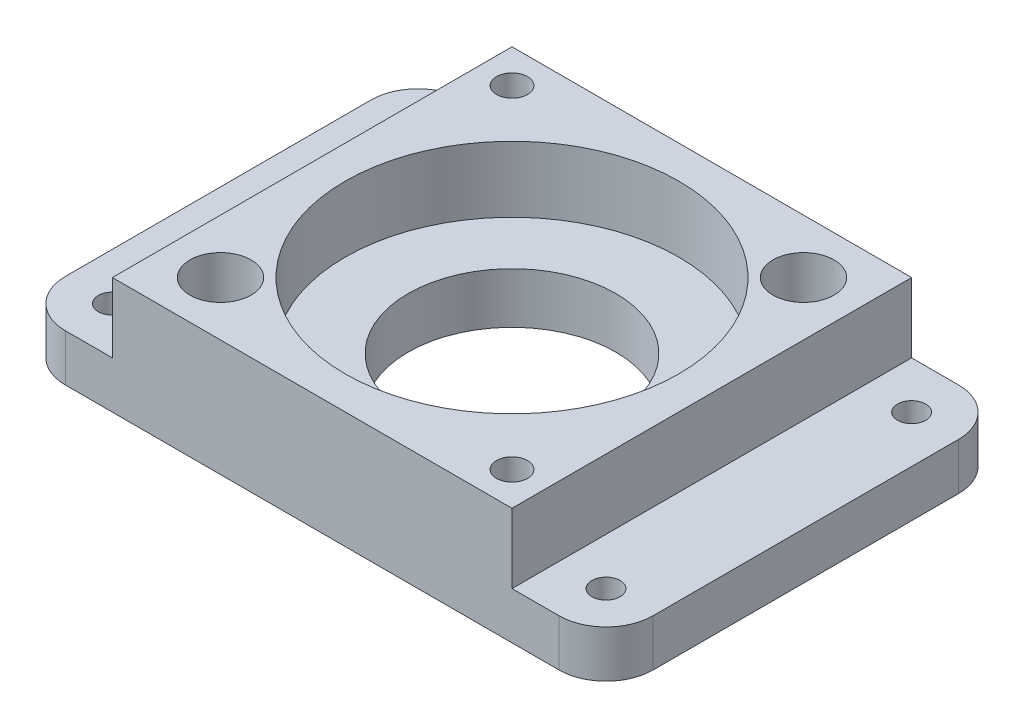
SolidWorks part; units mm, degrees
ref_plane "前视基准面" through (0, 0, 0) normal (0, 0, 1) x (1, 0, 0)
ref_plane "上视基准面" through (0, 0, 0) normal (0, 1, 0) x (1, 0, 0)
ref_plane "右视基准面" through (0, 0, 0) normal (1, 0, 0) x (0, 0, -1)
sketch "草图1" plane through (0, 0, 0) normal (0, 1, 0) x (1, 0, 0)
  line L1 (0, 0) -> (42.5, 0)
  line L2 (0, 0) -> (0, 42.5)
  line L3 (0, 42.5) -> (42.5, 42.5)
  line L4 (42.5, 0) -> (42.5, 42.5)
  dimension "D1" = 42.5
extrude "凸台-拉伸1" add sketch "草图1" along normal blind 12.4 contours L1 L4 L3 L2 region at (21.25, 0, -21.25)
sketch "草图2" plane through (0, 12.4, 0) normal (0, 1, 0) x (1, 0, 0)
  line L0 (0, 21.25) -> (42.5, 21.25) construction
  line L1 (0, 0) -> (0, 42.5) construction
  line L2 (42.5, 0) -> (42.5, 42.5) construction
  circle A0 centre (21.25, 21.25) radius 17.75
  dimension "D1" = 35.5
extrude "切除-拉伸1" cut sketch "草图2" against normal blind 7
sketch "草图3" plane through (0, 5.4, 0) normal (0, 1, 0) x (1, 0, 0)
  circle A0 centre (21.25, 21.25) radius 11.05
  dimension "D1" = 22.1
extrude "切除-拉伸2" cut sketch "草图3" against normal through all
sketch "草图4" plane through (0, 12.4, 0) normal (0, 1, 0) x (1, 0, 0)
  line L0 (21.25, 21.25) -> (0, 42.5) construction
  line L2 (21.25, 21.25) -> (38.9277, 3.5723) construction
  line L4 (5.75, 5.75) -> (36.75, 5.75) construction
  line L5 (5.75, 5.75) -> (5.75, 36.75) construction
  line L6 (5.75, 36.75) -> (36.75, 36.75) construction
  line L7 (36.75, 5.75) -> (36.75, 36.75) construction
  line L8 (5.75, 5.75) -> (36.75, 36.75) construction
  line L9 (5.75, 36.75) -> (36.75, 5.75) construction
  circle A0 centre (21.25, 21.25) radius 25 construction
  circle A1 centre (3.5723, 38.9277) radius 1.65
  circle A2 centre (38.9277, 3.5723) radius 1.65
  circle A3 centre (36.75, 36.75) radius 3.25
  circle A4 centre (5.75, 5.75) radius 3.25
  circle A5 centre (5.75, 5.75) radius 1.525
  circle A6 centre (36.75, 36.75) radius 1.525
  dimension "D1" = 50
  dimension "D2" = 3.3
  dimension "D5" = 6.5
  dimension "D6" = 3.05
  dimension "D4" = 31
  dimension "D3" = 2
extrude "切除-拉伸3" cut sketch "草图4" against normal blind 10 contours A4 A5 | A5 | A6 | A3 A6 region at (33.5919, 12.4, -36.75) region at (2.5919, 12.4, -5.75) region at (5.75, 12.4, -5.75) region at (36.75, 12.4, -36.75)
extrude "切除-拉伸4" cut sketch "草图4<3>" against normal through all contours A5 | A2 | A6 | A1 region at (3.5723, 12.4, -38.9277) region at (38.9277, 12.4, -3.5723) region at (5.75, 12.4, -5.75) region at (36.75, 12.4, -36.75)
sketch "草图4<3>" plane through (0, 12.4, 0) normal (0, 1, 0) x (1, 0, 0) same geometry as "草图4"
sketch "草图5" plane through (0, 0, 0) normal (0, -1, 0) x (1, 0, 0)
  line L0 (-5, 0) -> (-5, -5) construction
  line L1 (0, 0) -> (-10, 0)
  line L2 (0, 0) -> (0, -42.5)
  line L3 (0, -42.5) -> (-10, -42.5)
  line L4 (-10, 0) -> (-10, -42.5)
  line L5 (42.5, 0) -> (52.5, 0)
  line L6 (42.5, 0) -> (42.5, -42.5)
  line L7 (42.5, -42.5) -> (52.5, -42.5)
  line L8 (52.5, 0) -> (52.5, -42.5)
  line L9 (-5, -5) -> (-5, -37.5) construction
  line L10 (-5, -37.5) -> (-5, -42.5) construction
  line L11 (47.5, 0) -> (47.5, -5) construction
  line L12 (47.5, -5) -> (47.5, -37.5) construction
  line L13 (47.5, -37.5) -> (47.5, -42.5) construction
  circle A0 centre (-5, -5) radius 1.5
  circle A1 centre (-5, -37.5) radius 1.5
  circle A2 centre (47.5, -37.5) radius 1.5
  circle A3 centre (47.5, -5) radius 1.5
  dimension "D3" = 3
  dimension "D1" = 10
  dimension "D2" = 5
extrude "凸台-拉伸2" add sketch "草图5" against normal blind 5
fillet "圆角1" radius 5 4 edges at (-10, 2.5, 0) (52.5, 2.5, 0) (52.5, 2.5, -42.5) (-10, 2.5, -42.5)
